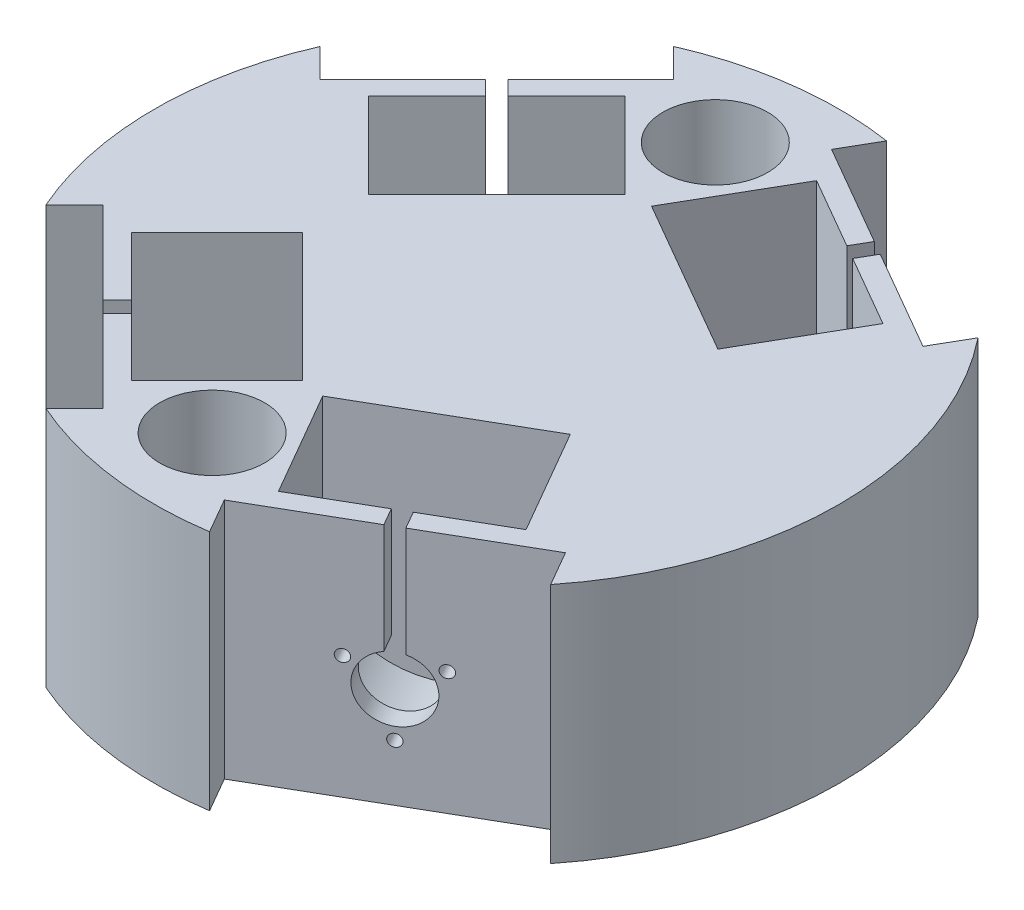
SolidWorks part; units mm, degrees
note: The reader was unsure of these and kept them because the rebuilt part matched: shared geometry of "Esboço3<10>".
ref_plane "Plano frontal" through (0, 0, 0) normal (0, 0, 1) x (1, 0, 0)
ref_plane "Plano superior" through (0, 0, 0) normal (0, 1, 0) x (1, 0, 0)
ref_plane "Plano direito" through (0, 0, 0) normal (1, 0, 0) x (0, 0, -1)
sketch "Esboço1" plane through (0, 0, 0) normal (0, 1, 0) x (1, 0, 0)
  line L0 (0, -20.0389) -> (0, 0) construction
  line L1 (0, 0) -> (-50000, 0) construction
  line L2 (0, 0) -> (-35355.3391, -35355.3391) construction
  line L3 (-77.8846, -34.044) -> (-34.044, -77.8846) construction
  line L4 (12.7259, -84.042) -> (66.4195, -53.042) construction
  line L5 (0, 0) -> (25000, -43301.2702) construction
  line L6 (12.7259, 84.042) -> (66.4195, 53.042) construction
  line L7 (-77.8846, 34.044) -> (-34.044, 77.8846) construction
  line L10 (-70.8135, -26.9729) -> (-26.9729, -70.8135)
  line L15 (-70.8135, -26.9729) -> (-77.8846, -34.044)
  line L16 (-26.9729, -70.8135) -> (-34.044, -77.8846)
  line L17 (7.7259, -75.3817) -> (61.4195, -44.3817)
  line L18 (66.4195, -53.042) -> (61.4195, -44.3817)
  line L19 (12.7259, -84.042) -> (7.7259, -75.3817)
  line L20 (66.4195, 53.042) -> (61.4195, 44.3817)
  line L21 (7.7259, 75.3817) -> (61.4195, 44.3817)
  line L22 (12.7259, 84.042) -> (7.7259, 75.3817)
  line L23 (-26.9729, 70.8135) -> (-34.044, 77.8846)
  line L24 (-70.8135, 26.9729) -> (-26.9729, 70.8135)
  line L25 (-70.8135, 26.9729) -> (-77.8846, 34.044)
  arc A0 (-34.044, -77.8846) -> (12.7259, -84.042) centre (0, 0) ccw
  arc A1 (66.4195, -53.042) -> (66.4195, 53.042) centre (0, 0) ccw
  arc A2 (-77.8846, 34.044) -> (-77.8846, -34.044) centre (0, 0) ccw
  arc A3 (12.7259, 84.042) -> (-34.044, 77.8846) centre (0, 0) ccw
  point P6 (0, 0)
  point P13 (-55.9643, -55.9643)
  point P17 (39.5727, -68.542)
  point P48 (-48.8932, -48.8932)
  point P51 (34.5727, -59.8817)
  point P52 (-74.3491, -30.5084)
  point P57 (-74.3491, 30.5084)
  dimension "D1" = 170
  dimension "D2" = 45
  dimension "D3" = 62
  dimension "D4" = 30
extrude "Base" add sketch "Esboço1" along normal blind 60
sketch "Esboço3" plane through (-48.8932, 0, 48.8932) normal (-0.7071, 0, 0.7071) x (0.7071, 0, 0.7071)
  line L0 (0, 0) -> (0, 60) construction
  line L1 (-31, 0) -> (31, 0) construction
  line L2 (-31, 60) -> (31, 60) construction
  line L3 (-2, 25) -> (2, 25)
  line L4 (-22.5, 25) -> (22.5, 25)
  line L5 (-22.5, 25) -> (-22.5, 80)
  line L6 (-22.5, 80) -> (22.5, 80)
  line L7 (22.5, 25) -> (22.5, 80)
  line L8 (-22.5, 25) -> (22.5, 80) construction
  line L9 (-22.5, 80) -> (22.5, 25) construction
  line L10 (-2, 25) -> (-2, 70)
  line L11 (2, 25) -> (2, 70)
  line L12 (-2, 70) -> (2, 70)
  arc A0 (-22.5, 25) -> (22.5, 25) centre (0, 25) ccw
  circle A1 centre (0, 25) radius 2
  circle A2 centre (0, 14) radius 1.5
  circle A3 centre (-9.5263, 30.5) radius 1.5
  circle A4 centre (9.5263, 30.5) radius 1.5
  circle A5 centre (0, 25) radius 8
  point P12 (0, 52.5)
  point P22 (0, 25)
  line M3 (31, 60) -> (-31, 60)
  dimension "D1" = 45
  dimension "D4" = 11
  dimension "D5" = 3
  dimension "D8" = 16
  dimension "D2" = 25
  dimension "D3" = 55
  dimension "D7" = 45
  dimension "D6" = 3
  dimension "4mm eixomotor" = 4
extrude "Motor-traseiro" cut sketch "Esboço3" against normal blind 30 from offset 5 contours L4 A1 | L4 A1 | L12 L10 L11 M3 | A1 L11 L10 M3 | A1 L4 A0 A2 | L4 A5 A1 offset against normal yes
extrude "Motor-eixo" cut sketch "Esboço3<10>" against normal blind 25 contours L4 A1 | L4 A1 | L4 A5 A1 | L4 A5 L11 | L10 A5 L4 | A4 | A2 | A3
sketch "Esboço3<10>" plane through (-48.8932, 0, 48.8932) normal (-0.7071, 0, 0.7071) x (0.7071, 0, 0.7071) same geometry as "Esboço3"
pattern_circular "PadrãoCircular1" count 2 every 285 about axis through (0, 60, 0) along (0, -1, 0) of "Motor-traseiro", "Motor-eixo"
mirror "Espelhar3" about plane through (0, 0, 0) normal (0, 0, 1) of "PadrãoCircular1", "Motor-eixo", "Motor-traseiro"
sketch "Esboço16" plane through (0, 60, 0) normal (0, 1, 0) x (1, 0, 0)
  line L0 (116.6673, 0) -> (-116.6673, 0) construction
  line L1 (-130.5262, -991.4449) -> (6395.7834, 48580.7982) construction
  circle A0 centre (-8.2232, -62.461) radius 13
  circle A1 centre (-8.2232, 62.461) radius 13
  point P4 (0, 0)
  point P8 (0, 0)
  dimension "D3" = 26
  dimension "D1" = 97.5
  dimension "D2" = 63
extrude "Capacitores" cut sketch "Esboço16" against normal blind 45
sketch "Esboço17" plane through (0, 0, 0) normal (0, -1, 0) x (1, 0, 0)
  line L1 (-27.6814, -14.4108) -> (22.8186, -14.4108)
  line L2 (-27.6814, -14.4108) -> (-27.6814, 25.4892)
  line L3 (-27.6814, 25.4892) -> (22.8186, 25.4892)
  line L4 (22.8186, -14.4108) -> (22.8186, 25.4892)
  line L5 (-27.6814, -14.4108) -> (22.8186, 25.4892) construction
  line L6 (-27.6814, 25.4892) -> (22.8186, -14.4108) construction
  point P4 (-2.4314, 5.5392)
  dimension "D1" = 50.5
  dimension "D2" = 39.9
